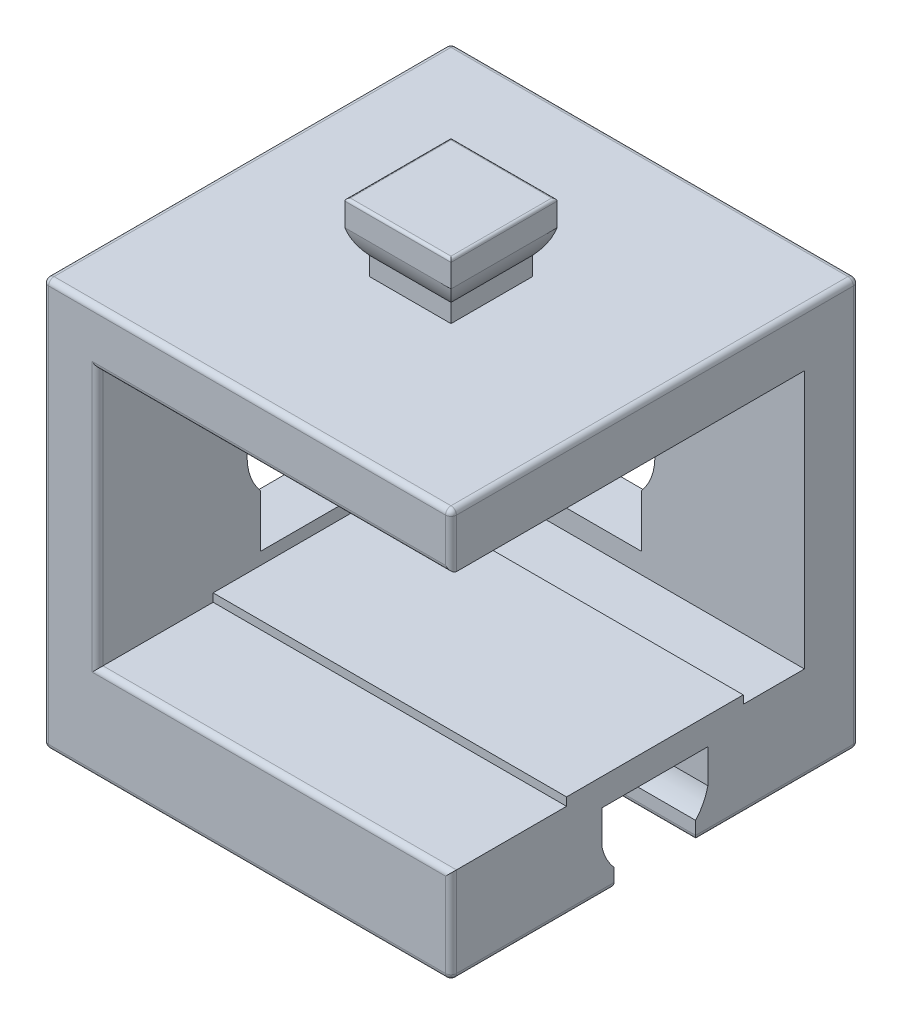
SolidWorks part; units mm, degrees
ref_plane "前视基准面" through (0, 0, 0) normal (0, 0, 1) x (1, 0, 0)
ref_plane "上视基准面" through (0, 0, 0) normal (0, 1, 0) x (1, 0, 0)
ref_plane "右视基准面" through (0, 0, 0) normal (1, 0, 0) x (0, 0, -1)
sketch "草图1" plane through (0, 0, 0) normal (0, 0, 1) x (1, 0, 0)
  line L1 (-7.5, 0) -> (7.5, 0)
  line L2 (-7.5, 0) -> (-7.5, 15)
  line L3 (-7.5, 15) -> (7.5, 15)
  line L4 (7.5, 0) -> (7.5, 15)
extrude "凸台-拉伸1" add sketch "草图1" along normal blind 7.5 and the other way blind 7.5
sketch "草图2" plane through (0, 0, 7.5) normal (0, 0, 1) x (1, 0, 0)
  line L0 (7.5, 0) -> (7.5, 15) construction
  line L1 (-5.5, 3.5) -> (7.5, 3.5)
  line L2 (-5.5, 3.5) -> (-5.5, 13)
  line L3 (-5.5, 13) -> (7.5, 13)
  line L4 (7.5, 3.5) -> (7.5, 13)
extrude "切除-拉伸1" cut sketch "草图2" against normal blind 13
sketch "草图3" plane through (0, 15, 0) normal (0, 1, 0) x (-1, 0, 0)
  line L1 (1.5, -1.5) -> (-1.5, -1.5)
  line L2 (1.5, -1.5) -> (1.5, 1.5)
  line L3 (1.5, 1.5) -> (-1.5, 1.5)
  line L4 (-1.5, -1.5) -> (-1.5, 1.5)
extrude "凸台-拉伸2" add sketch "草图3" along normal blind 1
sketch "草图4" plane through (0, 0, 0) normal (0, 0, 1) x (1, 0, 0)
  line L0 (-1.95, 17.5) -> (-1.95, 16.5556)
  line L2 (1.95, 17.5) -> (1.95, 16.5556)
  line L3 (-1.95, 17.5) -> (1.95, 17.5)
  line L5 (-1.5, 16) -> (-1.5, 15) construction
  line L6 (-1.5, 15.6771) -> (1.5, 15.6771)
  arc A0 (-1.95, 16.5556) -> (-1.5, 15.6771) centre (0, 17) ccw
  arc A1 (1.5, 15.6771) -> (1.95, 16.5556) centre (0, 17) ccw
extrude "凸台-拉伸3" add sketch "草图4" along normal blind 2 and the other way blind 2
sketch "草图5" plane through (-1.95, 0, 0) normal (-1, 0, 0) x (0, 0, 1)
  line L0 (-1.95, 17.5) -> (-1.95, 16.5556)
  line L1 (-2, 17.5) -> (-1.95, 17.5)
  line L2 (-2, 17.5) -> (-2, 15.6771)
  line L3 (-2, 15.6771) -> (-1.5, 15.6771)
  line L4 (2, 17.5) -> (2, 15.6771)
  line L5 (1.95, 17.5) -> (1.95, 16.5556)
  line L6 (1.5, 15.6771) -> (2, 15.6771)
  line L7 (1.95, 17.5) -> (2, 17.5)
  arc A0 (1.5, 15.6771) -> (1.95, 16.5556) centre (0, 17) ccw
  arc A1 (-1.95, 16.5556) -> (-1.5, 15.6771) centre (0, 17) ccw
extrude "切除-拉伸2" cut sketch "草图5" against normal up to next
sketch "草图6" plane through (7.5, 0, 0) normal (1, 0, 0) x (0, 0, -1)
  line L0 (5.5, 3.5) -> (-7.5, 3.5) construction
  line L1 (-3.25, 3.5) -> (3.25, 3.5)
  line L2 (-3.25, 3.5) -> (-3.25, 3.8)
  line L3 (-3.25, 3.8) -> (3.25, 3.8)
  line L4 (3.25, 3.5) -> (3.25, 3.8)
extrude "凸台-拉伸4" add sketch "草图6" against normal up to next
sketch "草图7" plane through (7.5, 0, 0) normal (1, 0, 0) x (0, 0, -1)
  line L0 (7.5, 0) -> (-7.5, 0) construction
  line L1 (-1.5, 0) -> (1.5, 0)
  line L2 (-1.5, 0) -> (-1.5, 0.6771)
  line L4 (1.5, 0) -> (1.5, 0.6771)
  line L5 (-1.95, 2.8) -> (1.95, 2.8)
  line L6 (-1.95, 2.8) -> (-1.95, 1.5556)
  line L7 (1.95, 2.8) -> (1.95, 1.5556)
  arc A0 (1.5, 0.6771) -> (1.95, 1.5556) centre (0, 2) ccw
  arc A1 (-1.95, 1.5556) -> (-1.5, 0.6771) centre (0, 2) ccw
extrude "切除-拉伸3" cut sketch "草图7" against normal blind 9.45
sketch "草图8" plane through (0, 0, -5.5) normal (0, 0, 1) x (1, 0, 0)
  line L0 (-1.5, 8.8229) -> (-1.5, 10.75)
  line L1 (-1.5, 4.25) -> (1.5, 4.25)
  line L2 (-1.5, 4.25) -> (-1.5, 6.1771)
  line L3 (-1.5, 10.75) -> (1.5, 10.75)
  line L4 (1.5, 4.25) -> (1.5, 6.1771)
  line L5 (1.5, 8.8229) -> (1.5, 10.75)
  arc A0 (-1.5, 8.8229) -> (-1.5, 6.1771) centre (0, 7.5) ccw
  arc A1 (1.5, 6.1771) -> (1.5, 8.8229) centre (0, 7.5) ccw
extrude "切除-拉伸4" cut sketch "草图8" against normal up to next
sketch "草图9" plane through (-5.5, 0, 0) normal (1, 0, 0) x (0, 0, -1)
  line L0 (-1.5, 8.8229) -> (-1.5, 10.75)
  line L1 (-1.5, 4.25) -> (1.5, 4.25)
  line L2 (-1.5, 4.25) -> (-1.5, 6.1771)
  line L3 (-1.5, 10.75) -> (1.5, 10.75)
  line L4 (1.5, 4.25) -> (1.5, 6.1771)
  line L5 (1.5, 8.8229) -> (1.5, 10.75)
  arc A0 (-1.5, 8.8229) -> (-1.5, 6.1771) centre (0, 7.5) ccw
  arc A1 (1.5, 6.1771) -> (1.5, 8.8229) centre (0, 7.5) ccw
extrude "切除-拉伸5" cut sketch "草图9" against normal up to next
fillet "圆角1" radius 0.1 4 edges at (-1.95, 17.5, 0) (0, 17.5, -1.95) (1.95, 17.5, 0) (0, 17.5, 1.95)
fillet "圆角2" radius 0.2 20 edges at (7.5, 0, -4.5) (0, 0, -7.5) (-7.5, 0, 0) (7.5, 0, 4.5) (2.775, 0, 1.5) (-1.95, 0, 0) (2.775, 0, -1.5) (1, 3.5, 7.5) (7.5, 1.75, 7.5) (0, 0, 7.5) (-7.5, 7.5, 7.5) (0, 15, 7.5) (7.5, 14, 7.5) (1, 13, 7.5) (-5.5, 8.25, 7.5) (7.5, 7.5, -7.5) (7.5, 15, 0) (0, 15, -7.5) (-7.5, 15, 0) (-7.5, 7.5, -7.5)
